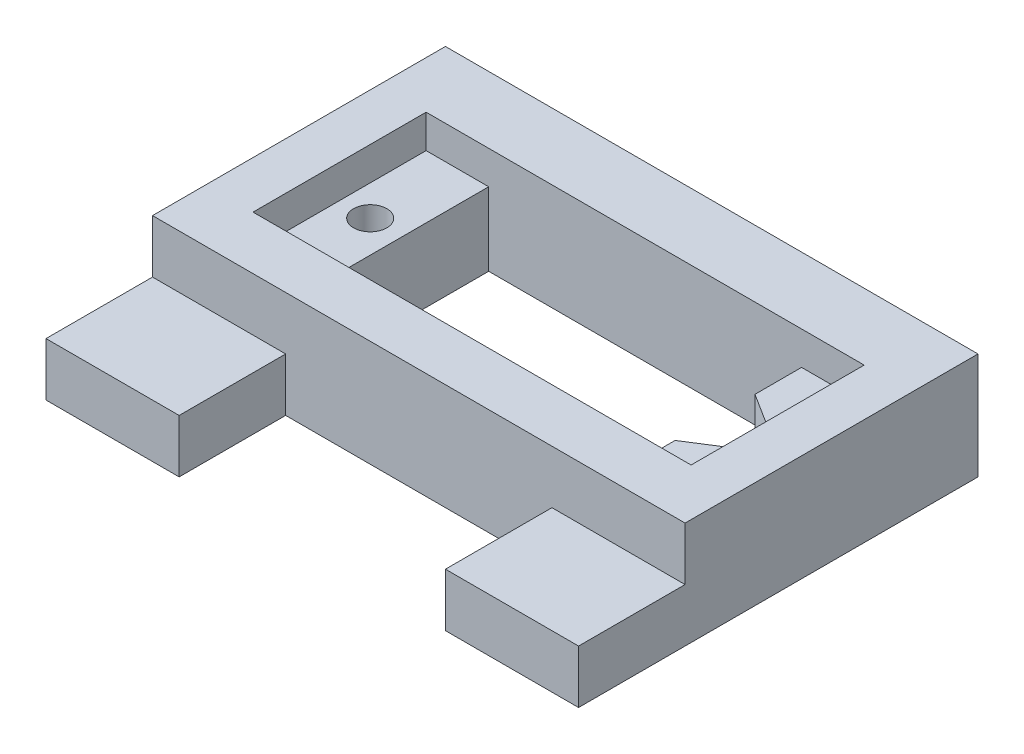
SolidWorks part; units mm, degrees
ref_plane "Front Plane" through (0, 0, 0) normal (0, 0, 1) x (1, 0, 0)
ref_plane "Top Plane" through (0, 0, 0) normal (0, 1, 0) x (1, 0, 0)
ref_plane "Right Plane" through (0, 0, 0) normal (1, 0, 0) x (0, 0, -1)
sketch "Sketch1" plane through (0, 0, 0) normal (0, 1, 0) x (1, 0, 0)
  line L0 (11.75, 13) -> (11.75, 0) construction
  line L1 (0, 0) -> (23.5, 0)
  line L2 (0, 0) -> (0, 13)
  line L3 (0, 13) -> (23.5, 13)
  line L4 (23.5, 0) -> (23.5, 13)
  line L5 (-8.25, 18) -> (31.75, 18)
  line L6 (-8.25, 18) -> (-8.25, -4)
  line L7 (1.75, -12) -> (21.75, -12)
  line L8 (31.75, 18) -> (31.75, -4)
  line L9 (-8.25, -4) -> (-8.25, -12)
  line L18 (-8.25, -12) -> (1.75, -12)
  line L19 (31.75, -4) -> (31.75, -12)
  line L20 (31.75, -12) -> (21.75, -12)
  dimension "D1" = 13
  dimension "D2" = 23.5
  dimension "D3" = 22
  dimension "D4" = 30
  dimension "D5" = 20
  dimension "D6" = 22
  dimension "D7" = 40
  dimension "D10" = 12
extrude "Boss-Extrude1" add sketch "Sketch1" along normal blind 8
sketch "Sketch2" plane through (0, 8, 0) normal (0, 1, 0) x (1, 0, 0)
  line L0 (31.75, -12) -> (31.75, 18) construction
  line L1 (-8.25, -12) -> (31.75, -12)
  line L2 (-8.25, -12) -> (-8.25, -4)
  line L3 (-8.25, -4) -> (31.75, -4)
  line L4 (31.75, -12) -> (31.75, -4)
  dimension "D1" = 8
extrude "Cut-Extrude1" cut sketch "Sketch2" against normal blind 4
sketch "Sketch3" plane through (0, 4, 0) normal (0, 1, 0) x (1, 0, 0)
  line L0 (31.75, -4) -> (-8.25, -4) construction
  line L1 (1.75, -4) -> (21.75, -4)
  line L2 (1.75, -4) -> (1.75, -12)
  line L3 (1.75, -12) -> (21.75, -12)
  line L4 (21.75, -4) -> (21.75, -12)
  line L5 (-8.25, -12) -> (31.75, -12) construction
  line L6 (31.75, -12) -> (31.75, -4) construction
  dimension "D1" = 10
  dimension "D2" = 10
extrude "Cut-Extrude2" cut sketch "Sketch3" against normal through all both and the other way through all
sketch "Sketch4" plane through (0, 8, 0) normal (0, 1, 0) x (1, 0, 0)
  line L0 (0, 13) -> (-4.7, 13)
  line L1 (-4.7, 13) -> (-4.7, 0)
  line L2 (-4.7, 0) -> (0, 0)
  line L3 (11.75, 13) -> (11.75, 0) construction
  line L4 (23.5, 13) -> (0, 13) construction
  line L5 (0, 0) -> (23.5, 0) construction
  line L6 (28.2, 0) -> (23.5, 0)
  line L7 (28.2, 13) -> (28.2, 0)
  line L8 (23.5, 13) -> (28.2, 13)
  line L9 (0, 13) -> (0, 0)
  line L10 (23.5, 13) -> (23.5, 0)
  circle A0 centre (-2.4, 6.5) radius 1.25
  circle A1 centre (25.9, 6.5) radius 1.25
  dimension "D2" = 2.3
  dimension "D3" = 2.5
  dimension "D1" = 4.7
  dimension "D4" = 6.5
extrude "Cut-Extrude3" cut sketch "Sketch4" against normal blind 2.5
sketch "Sketch5" plane through (0, 8, 0) normal (0, 1, 0) x (1, 0, 0)
  circle A0 centre (-2.4, 6.5) radius 1.25
  circle A1 centre (25.9, 6.5) radius 1.25
extrude "Cut-Extrude4" cut sketch "Sketch5" against normal through all both and the other way through all
sketch "Sketch6" plane through (0, 5.5, 0) normal (0, 1, 0) x (1, 0, 0)
  line L0 (23.5, 9.5) -> (26.5689, 7.556)
  line L1 (23.5, 13) -> (23.5, 0) construction
  line L2 (23.5, 3.5) -> (26.5689, 5.444)
  line L3 (23.5, 9.5) -> (23.5, 3.5)
  arc A0 (26.5689, 5.444) -> (26.5689, 7.556) centre (25.9, 6.5) ccw
  dimension "D1" = 3
  dimension "D3" = 2.5
  dimension "D2" = 3
extrude "Cut-Extrude5" cut sketch "Sketch6" against normal through all both and the other way through all
